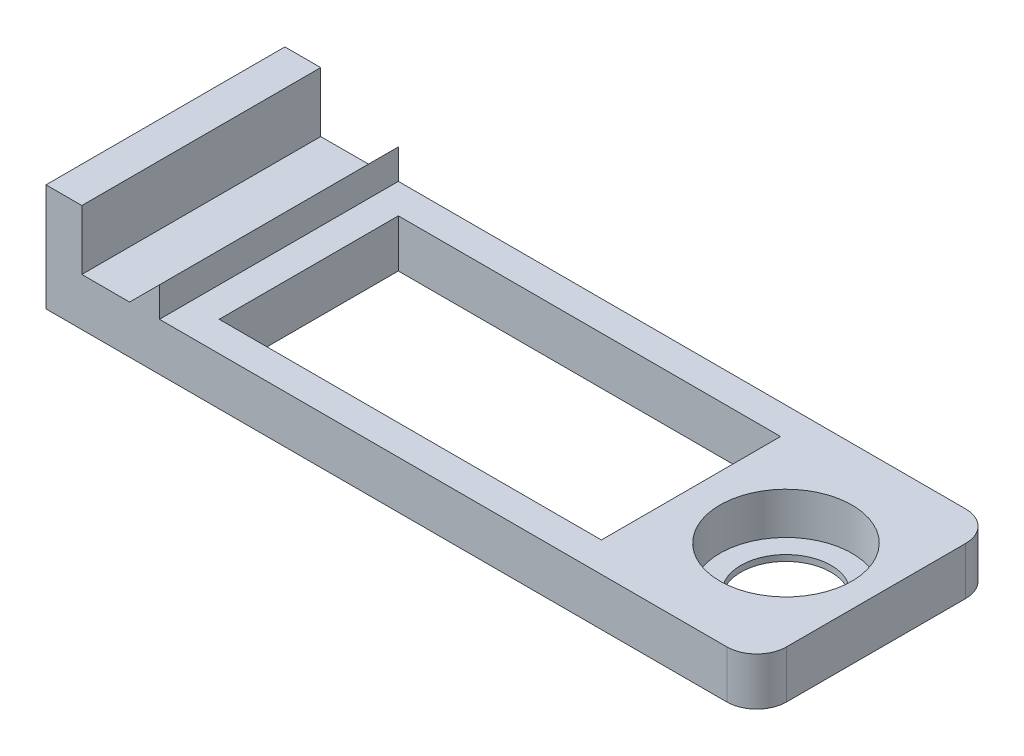
SolidWorks part; units mm, degrees
ref_plane "Front Plane" through (0, 0, 0) normal (0, 0, 1) x (1, 0, 0)
ref_plane "Top Plane" through (0, 0, 0) normal (0, 1, 0) x (1, 0, 0)
ref_plane "Right Plane" through (0, 0, 0) normal (1, 0, 0) x (0, 0, -1)
sketch "Sketch1" plane through (0, 0, 0) normal (0, 1, 0) x (1, 0, 0)
  line L1 (-59.5, -20) -> (59.5, -20)
  line L2 (-59.5, -20) -> (-59.5, 20)
  line L3 (-59.5, 20) -> (59.5, 20)
  line L4 (59.5, -20) -> (59.5, 20)
  line L5 (-59.5, -20) -> (59.5, 20) construction
  line L6 (-59.5, 20) -> (59.5, -20) construction
  point P0 (0, 0)
  dimension "D1" = 119
  dimension "D2" = 40
extrude "Boss-Extrude1" add sketch "Sketch1" along normal blind 8
sketch "Sketch2" plane through (0, 8, 0) normal (0, 1, 0) x (1, 0, 0)
  line L0 (59.5, 0) -> (44.4, 0) construction
  line L1 (59.5, -20) -> (59.5, 20) construction
  circle A0 centre (44.4, 0) radius 11.05
  dimension "D2" = 22.1
  dimension "D1" = 15.1
extrude "Cut-Extrude1" cut sketch "Sketch2" against normal blind 7
sketch "Sketch3" plane through (0, 0, 0) normal (0, -1, 0) x (1, 0, 0)
  line L0 (59.5, 0) -> (44.4, 0) construction
  line L1 (59.5, 20) -> (59.5, -20) construction
  circle A0 centre (44.4, 0) radius 7.55
  dimension "D2" = 15.1
  dimension "D1" = 15.1
extrude "Cut-Extrude2" cut sketch "Sketch3" against normal up to next
sketch "Sketch4" plane through (0, 8, 0) normal (0, 1, 0) x (1, 0, 0)
  line L0 (-59.5, -20) -> (59.5, -20) construction
  line L1 (-59.5, 20) -> (-53.5, 20)
  line L2 (-59.5, 20) -> (-59.5, -20)
  line L3 (-59.5, -20) -> (-53.5, -20)
  line L4 (-53.5, 20) -> (-53.5, -20)
  dimension "D1" = 6
extrude "Boss-Extrude2" add sketch "Sketch4" along normal blind 10
sketch "Sketch6" plane through (0, 0, 20) normal (0, 0, 1) x (1, 0, 0)
  line L0 (-59.5, 8) -> (-40.5, 8) construction
  line L1 (-59.5, 18) -> (-59.5, 0) construction
  line L2 (-53.5, 8) -> (59.5, 8) construction
  line L3 (-40.5, 8) -> (-40.5, 13)
  line L4 (-40.5, 13) -> (-45.5, 8)
  line L5 (-45.5, 8) -> (-40.5, 8)
  dimension "D1" = 19
  dimension "D2" = 5
  dimension "D3" = 5
extrude "Boss-Extrude3" add sketch "Sketch6" against normal blind 40
fillet "Fillet1" radius 5 2 edges at (59.5, 4, 20) (59.5, 4, -20)
sketch "Sketch7" plane through (0, 8, 0) normal (0, 1, 0) x (1, 0, 0)
  line L0 (-40.5, 15) -> (-35.5, 15) construction
  line L1 (-40.5, 20) -> (-40.5, -20) construction
  line L2 (-35.5, 15) -> (-35.5, 20) construction
  line L3 (54.5, 20) -> (-40.5, 20) construction
  line L5 (-35.5, 15) -> (28.5, 15)
  line L6 (-35.5, 15) -> (-35.5, -15)
  line L7 (-35.5, -15) -> (28.5, -15)
  line L8 (28.5, 15) -> (28.5, -15)
  dimension "D1" = 5
  dimension "D2" = 5
  dimension "D3" = 64
  dimension "D4" = 30
extrude "Cut-Extrude3" cut sketch "Sketch7" against normal up to next
